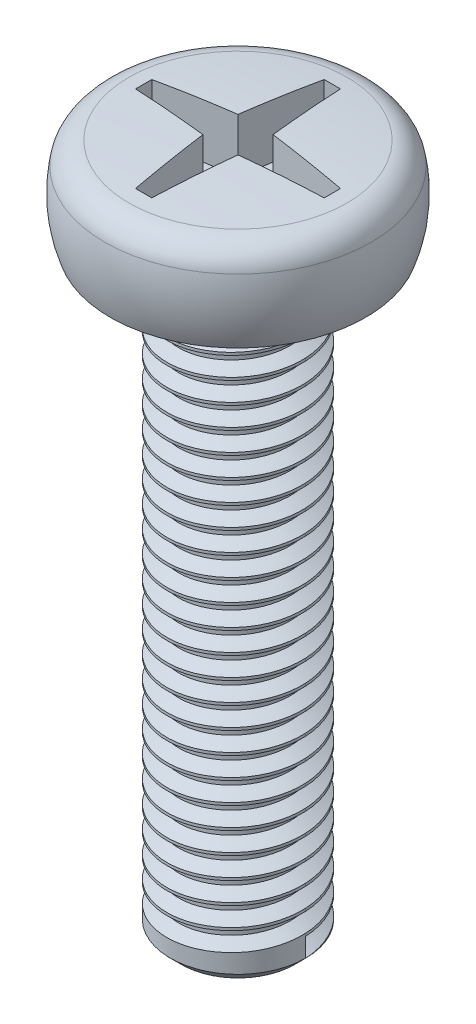
SolidWorks part; units mm, degrees
material "ASTM A36 Steel"
ref_plane "Front Plane" through (0, 0, 0) normal (0, 0, 1) x (1, 0, 0)
ref_plane "Top Plane" through (0, 0, 0) normal (0, 1, 0) x (1, 0, 0)
ref_plane "Right Plane" through (0, 0, 0) normal (1, 0, 0) x (0, 0, -1)
sketch "Sketch1" plane through (0, 0, 0) normal (0, 0, 1) x (1, 0, 0)
  line L0 (0, 3.2272) -> (0, -0.2728) construction
  line L1 (0, 3.2272) -> (5, 3.2272) construction
  line L2 (5, 3.2272) -> (5, -0.2728) construction
  line L3 (5, -0.2728) -> (0, -0.2728) construction
  line L4 (5, 1.4772) -> (0, 1.4772) construction
  line L5 (0, 2.9428) -> (4.7253, 2.9428) construction
  line L6 (4.7139, -0.2728) -> (0, -0.2728)
  line L7 (0, 3.2272) -> (0, -0.2728)
  arc A0 (4.7139, 2.9745) -> (0, 3.2272) centre (0, -40.8721) ccw
  arc A1 (4.7139, -0.2728) -> (4.7139, 2.9745) centre (0.2499, 1.3508) ccw
  point P11 (0, 1.4772)
  dimension "D1" = 3.5
  dimension "D2" = 5
revolve "Revolve1" add sketch "Sketch1" angle 360 about L7
fillet "Fillet1" radius 1 1 edges at (-4.7139, 2.9745, 0)
sketch "Sketch2" plane through (0, -0.2728, 0) normal (0, -1, 0) x (1, 0, 0)
  line L0 (0, 0) -> (0, -3.7135) construction
  line L1 (-0.3, -3.485) -> (0.3, -3.485)
  line L8 (0.3, -3.485) -> (0.6473, -0.6473)
  line L12 (-0.3, -3.485) -> (-0.6473, -0.6473)
  line L16 (-3.485, 0.3) -> (-3.485, -0.3)
  line L17 (-3.485, -0.3) -> (-0.6473, -0.6473)
  line L18 (-3.485, 0.3) -> (-0.6473, 0.6473)
  line L19 (0, 0) -> (-3.7135, 0) construction
  line L20 (0.3, 3.485) -> (-0.3, 3.485)
  line L21 (-0.3, 3.485) -> (-0.6473, 0.6473)
  line L22 (0.3, 3.485) -> (0.6473, 0.6473)
  line L23 (0, 0) -> (0, 3.7135) construction
  line L24 (3.485, -0.3) -> (3.485, 0.3)
  line L25 (3.485, 0.3) -> (0.6473, 0.6473)
  line L26 (3.485, -0.3) -> (0.6473, -0.6473)
  line L27 (0, 0) -> (3.7135, 0) construction
  point P6 (0, -3.485)
  point P15 (-3.485, 0)
  point P21 (0, 3.485)
  point P28 (3.485, 0)
  point P29 (0, 0)
  dimension "D1" = 0.3
  dimension "D2" = 4
extrude "Cut-Extrude1" cut sketch "Sketch2" along normal blind 2 from surface starting at face at (4.0261, 3.043, 0)
sketch "Sketch3" plane through (0, -0.2728, 0) normal (0, -1, 0) x (1, 0, 0)
  circle A0 centre (0, 0) radius 2.5
  dimension "D1" = 5
extrude "Boss-Extrude1" add sketch "Sketch3" along normal blind 22
chamfer "Chamfer1" distance 0.4 angle 45 1 edges at (2.5, -22.2728, 0)
thread "Thread1" pitch 0.8 start angle 0, offset 0, length 0, pitch 0.8, diameter 5
ref_plane "Plane1" through (2.5, -21.8728, 0) normal (0, 0, 1) x (1, 0, 0)
sketch "Thread Profile1" plane through (2.5, -21.8728, 0) normal (0, 0, 1) x (1, 0, 0)
  line L0 (0, 0) -> (0, 0.8) construction
  line L11 (0, 0) -> (0, 0.7)
  line L12 (0, 0.7) -> (-0.433, 0.45)
  line L13 (-0.433, 0.45) -> (-0.433, 0.25)
  line L15 (-0.433, 0.25) -> (0, 0)
  line L17 (-0.433, 0.35) -> (0, 0.35) construction
  point P2 (0, 0)
  dimension "Pitch" = 0.8
  dimension "Profile_Angle" = 60
  dimension "Profile_Land" = 0.2
  dimension "Profile_Height" = 0.433
scale "Scale1" scale about centroid uniform scaling yes scale factor 0.6
